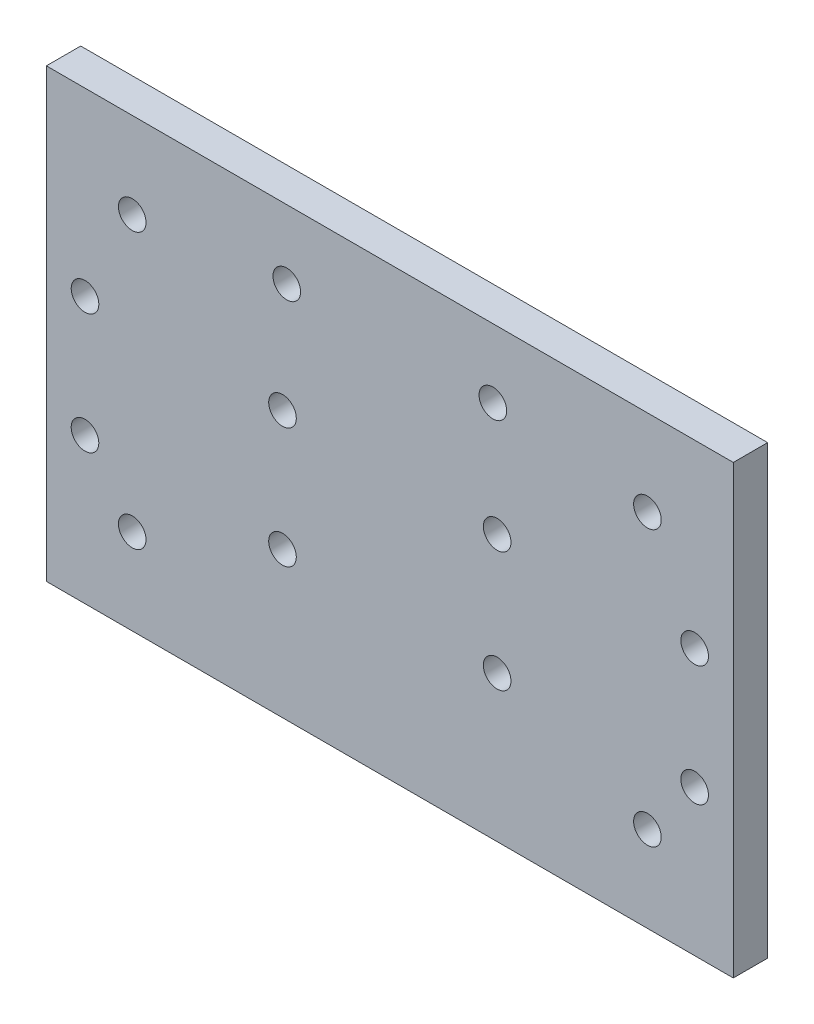
SolidWorks part; units mm, degrees
material "6061 Alloy"
ref_plane "Front Plane" through (0, 0, 0) normal (0, 0, 1) x (1, 0, 0)
ref_plane "Top Plane" through (0, 0, 0) normal (0, 1, 0) x (1, 0, 0)
ref_plane "Right Plane" through (0, 0, 0) normal (1, 0, 0) x (0, 0, -1)
sketch "Sketch1" plane through (0, 0, 0) normal (0, 0, 1) x (1, 0, 0)
  line L1 (-63.5, 41.275) -> (63.5, 41.275)
  line L2 (-63.5, 41.275) -> (-63.5, -41.275)
  line L3 (-63.5, -41.275) -> (63.5, -41.275)
  line L4 (63.5, 41.275) -> (63.5, -41.275)
  line L5 (-63.5, 41.275) -> (63.5, -41.275) construction
  line L6 (-63.5, -41.275) -> (63.5, 41.275) construction
  point P0 (0, 0)
  dimension "D1" = 127
  dimension "D2" = 82.55
extrude "Plate" add sketch "Sketch1" along normal blind 6.35
hole_wizard "Bearing/Nut Helicoil Holes" positions "Sketch3" profile "Sketch4" tap size "#10-32" standard "Helicoil® Inch" end condition up to next
sketch "Sketch3" plane through (0, 0, 0) normal (0, 0, -1) x (-1, 0, 0)
  line L1 (-56.3565, 7.9375) -> (-19.844, 7.9375) construction
  line L2 (-56.3565, 7.9375) -> (-56.3565, -14.2875) construction
  line L3 (-56.3565, -14.2875) -> (-19.844, -14.2875) construction
  line L4 (-19.844, 7.9375) -> (-19.844, -14.2875) construction
  line L6 (19.844, 7.9375) -> (56.3565, 7.9375) construction
  line L7 (19.844, 7.9375) -> (19.844, -14.2875) construction
  line L8 (19.844, -14.2875) -> (56.3565, -14.2875) construction
  line L9 (56.3565, 7.9375) -> (56.3565, -14.2875) construction
  line L10 (0, 0) -> (0, -3.175) construction
  line L12 (-19.844, -3.175) -> (19.844, -3.175) construction
  line L13 (0, 0) -> (0, 28.575) construction
  line L15 (-19.05, 28.575) -> (19.05, 28.575) construction
  line L16 (63.5, -41.275) -> (-63.5, -41.275) construction
  point P0 (-56.3565, 7.9375)
  point P1 (-19.844, -14.2875)
  point P138 (-56.3565, -14.2875)
  point P139 (-19.844, 7.9375)
  point P140 (19.844, 7.9375)
  point P141 (56.3565, -14.2875)
  point P310 (19.844, -14.2875)
  point P311 (56.3565, 7.9375)
  point P347 (-19.05, 28.575)
  point P348 (19.05, 28.575)
  dimension "D1" = 22.225
  dimension "D2" = 36.5125
  dimension "D3" = 39.688
  dimension "D4" = 38.1
  dimension "D5" = 31.75
  dimension "D6" = 26.9875
sketch "Sketch4" plane through (56.3565, 7.9375, 0) normal (1, 0, 0) x (0, 1, 0)
  line L0 (0, 0) -> (0, 6.35)
  line L1 (0, 6.35) -> (2.5527, 6.35)
  line L2 (2.5527, 6.35) -> (2.5527, 0)
  line L5 (2.5527, 0) -> (0, 0)
  line L11 (0, -6.35) -> (0, 107.95) construction
  dimension "Thru Tap Drill Dia." = 5.1054
  dimension "Thru Tap Drill Depth" = 6.35
cosmetic thread "Hole Thread1" parameters "D1"=5.588, "D2"=5.936
cosmetic thread "Hole Thread2" parameters "D1"=5.588, "D2"=5.936
cosmetic thread "Hole Thread3" parameters "D1"=5.588, "D2"=5.936
cosmetic thread "Hole Thread4" parameters "D1"=5.588, "D2"=5.936
cosmetic thread "Hole Thread5" parameters "D1"=5.588, "D2"=5.936
cosmetic thread "Hole Thread6" parameters "D1"=5.588, "D2"=5.936
cosmetic thread "Hole Thread7" parameters "D1"=5.588, "D2"=5.936
cosmetic thread "Hole Thread8" parameters "D1"=5.588, "D2"=5.936
cosmetic thread "Hole Thread9" parameters "D1"=5.588, "D2"=5.936
cosmetic thread "Hole Thread10" parameters "D1"=5.588, "D2"=5.936
hole_wizard "Router Mount Helicoil Holes" positions "Sketch6" profile "Sketch5" tap size "#10-32" standard "Helicoil® Inch" end condition up to next
sketch "Sketch6" plane through (0, 0, 0) normal (0, 0, -1) x (-1, 0, 0)
  line L1 (-47.625, 25.4) -> (47.625, 25.4) construction
  line L2 (-47.625, 25.4) -> (-47.625, -25.4) construction
  line L3 (-47.625, -25.4) -> (47.625, -25.4) construction
  line L4 (47.625, 25.4) -> (47.625, -25.4) construction
  line L5 (-47.625, -25.4) -> (47.625, 25.4) construction
  point P0 (-47.625, 25.4)
  point P1 (47.625, -25.4)
  point P190 (-47.625, -25.4)
  point P191 (47.625, 25.4)
  dimension "D1" = 50.8
  dimension "D2" = 95.25
cosmetic thread "Hole Thread13" parameters "D1"=5.588, "D2"=5.936
cosmetic thread "Hole Thread14" parameters "D1"=5.588, "D2"=5.936
cosmetic thread "Hole Thread15" parameters "D1"=5.588, "D2"=5.936
cosmetic thread "Hole Thread16" parameters "D1"=5.588, "D2"=5.936
sketch "Sketch5" plane through (47.625, 25.4, 0) normal (1, 0, 0) x (0, 1, 0)
  line L0 (0, 0) -> (0, 6.35)
  line L1 (0, 6.35) -> (2.5527, 6.35)
  line L2 (2.5527, 6.35) -> (2.5527, 0)
  line L5 (2.5527, 0) -> (0, 0)
  line L11 (0, -6.35) -> (0, 107.95) construction
  dimension "Thru Tap Drill Dia." = 5.1054
  dimension "Thru Tap Drill Depth" = 6.35
ref_plane "Plane1" through (0, -25.4, 0) normal (0, -1, 0) x (-1, 0, 0)
ref_plane "Plane2" through (0, 25.4, 0) normal (0, -1, 0) x (-1, 0, 0)
